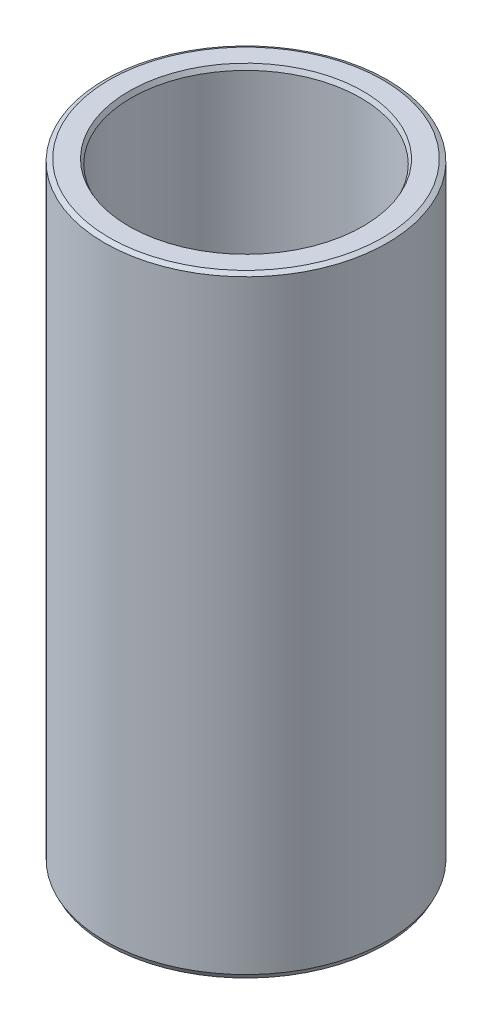
SolidWorks part; units mm, degrees
ref_plane "Front Plane" through (0, 0, 0) normal (0, 0, 1) x (1, 0, 0)
ref_plane "Top Plane" through (0, 0, 0) normal (0, 1, 0) x (1, 0, 0)
ref_plane "Right Plane" through (0, 0, 0) normal (1, 0, 0) x (0, 0, -1)
sketch "Sketch1" plane through (0, 0, 0) normal (0, 1, 0) x (1, 0, 0)
  circle A0 centre (0, 0) radius 45
  dimension "SLEEVE_OD" = 90
extrude "Boss-Extrude1" add sketch "Sketch1" along normal blind 194.5655
sketch "Sketch2" plane through (0, 0, 0) normal (0, 1, 0) x (1, 0, 0)
  circle A0 centre (0, 0) radius 36.5294
  dimension "BORE_D" = 73.0588
extrude "Cut-Extrude1" cut sketch "Sketch2" along normal through all
chamfer "Chamfer1" distance 0.7338 angle 63.536 4 edges at (0, 194.5655, 36.5294) (0, 0, 36.5294) (0, 0, 45) (0, 194.5655, 45) first distance on face at (0, 194.5655, 36.5294) first distance on face at (0, 0, 36.5294) first distance on face at (0, 194.5655, 45)
